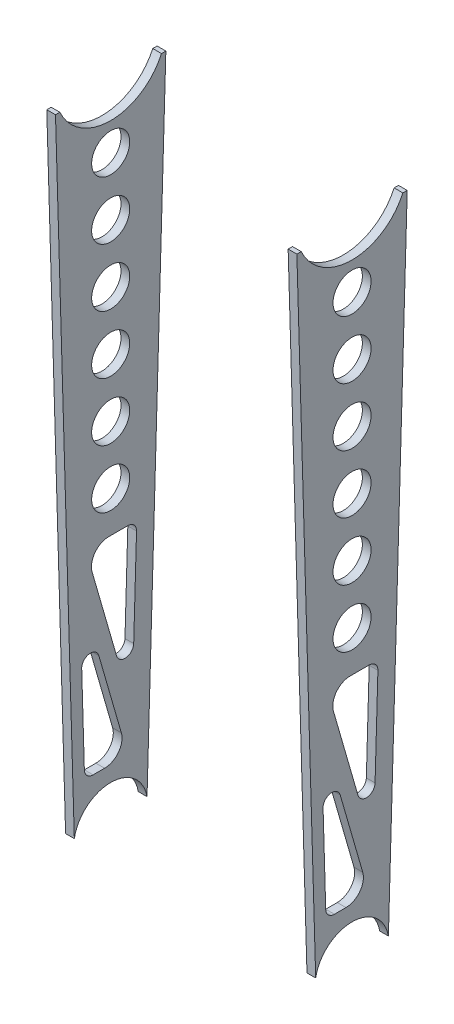
SolidWorks part; units mm, degrees
material "ASTM A36 Steel"
ref_plane "Front Plane" through (0, 0, 0) normal (0, 0, 1) x (1, 0, 0)
ref_plane "Top Plane" through (0, 0, 0) normal (0, 1, 0) x (1, 0, 0)
ref_plane "Right Plane" through (0, 0, 0) normal (1, 0, 0) x (0, 0, -1)
sketch "Sketch1" plane through (0, 0, 0) normal (1, 0, 0) x (0, 0, -1)
  line L0 (-18.9731, -7.9582) -> (-12.5024, -226.7686)
  line L1 (18.9731, -7.9582) -> (12.5024, -226.7686)
  line L2 (-18.9731, -7.9582) -> (-17.4731, -7.9582)
  line L3 (17.4731, -7.9582) -> (18.9731, -7.9582)
  line L4 (0, -22.2) -> (-29.8359, -22.2) construction
  line L5 (0, -19.2) -> (-29.8359, -19.2) construction
  line L10 (-4.0798, -176.4646) -> (3.6669, -203.3381)
  line L11 (-5.4127, -207.8826) -> (7.0583, -207.8826) construction
  line L12 (-5.4127, -207.8826) -> (-11.7157, -142.7546) construction
  line L13 (0, 0) -> (0, -210.55) construction
  line L14 (-11.7157, -142.7546) -> (8.9843, -142.7546) construction
  line L15 (7.0583, -207.8826) -> (8.9843, -142.7546) construction
  line L16 (-5.4127, -207.8826) -> (8.9843, -142.7546) construction
  line L17 (-11.7157, -142.7546) -> (7.0583, -207.8826) construction
  line L18 (-2.0984, -211) -> (-6.0544, -211)
  line L19 (-9.0531, -208.0887) -> (-9.9611, -177.3843)
  line L20 (-0.6196, -142.7546) -> (5.8945, -142.7546)
  line L21 (8.8929, -145.8431) -> (7.9159, -178.8818)
  line L22 (2.0346, -179.6241) -> (-6.3849, -150.4165)
  circle A0 centre (0, 0) radius 19.2 construction
  arc A1 (17.4731, -7.9582) -> (-17.4731, -7.9582) centre (0, 0) cw
  circle A2 centre (0, -48.7494) radius 6.5481
  circle A3 centre (0, -28.7481) radius 6.5481
  circle A6 centre (0, -68.7507) radius 6.5481
  circle A7 centre (0, -88.752) radius 6.5481
  circle A8 centre (0, -108.7533) radius 6.5481
  arc A9 (12.5024, -226.7686) -> (-12.5024, -226.7686) centre (0, -229) ccw
  circle A10 centre (0, -128.7546) radius 6.5481
  arc A11 (-4.0798, -176.4646) -> (-9.9611, -177.3843) centre (-6.9624, -177.2956) ccw
  arc A12 (-6.0544, -211) -> (-9.0531, -208.0887) centre (-6.0544, -208) cw
  arc A13 (3.6669, -203.3381) -> (-2.0984, -211) centre (-2.0984, -205) cw
  arc A14 (7.9159, -178.8818) -> (2.0346, -179.6241) centre (4.9172, -178.7932) cw
  arc A15 (5.8945, -142.7546) -> (8.8929, -145.8431) centre (5.8945, -145.7544) cw
  arc A16 (-0.6196, -142.7546) -> (-6.3849, -150.4165) centre (-0.6196, -148.7546) ccw
  point P5 (12.8535, -227.9864)
  point P36 (0, -183.3969)
  point P49 (-10.6637, -153.6246)
  point P55 (11.6666, -207.8826)
  point P58 (7.3488, -198.0594)
  point P64 (-8.5935, -142.7546)
  dimension "D1" = 38.4
  dimension "D2" = 3
  dimension "D4" = 13.0962
  dimension "D5" = 14
  dimension "D7" = 3
  dimension "D9" = 18
  dimension "D10" = 4
  dimension "D11" = 229
  dimension "D12" = 25.4
  dimension "D13" = 6
  dimension "D14" = 6
  dimension "D19" = 3
  dimension "D21" = 3
  dimension "D8" = 6
  dimension "D3" = 6
  dimension "D6" = 1.5
  dimension "D20" = 2
extrude "Boss-Extrude2" add sketch "Sketch1<2>" against normal blind 3 separate body
sketch "Sketch1<2>" plane through (0, 0, 0) normal (1, 0, 0) x (0, 0, -1) same geometry as "Sketch1"
extrude "Boss-Extrude1" add sketch "Sketch1" along normal blind 3 from offset 80 separate body
sketch "Sketch2" plane through (0, 0, 0) normal (1, 0, 0) x (0, 0, -1)
  circle A0 centre (0, -28.7481) radius 6.5481 construction
  circle A2 centre (0, -28.7481) radius 6.5481
extrude "Boss-ExtrudeUpperBolt" [suppressed] add sketch "Sketch2" along normal blind 102 and the other way blind 12 from offset 6 separate body offset against normal yes
sketch "Sketch4" plane through (0, 0, 0) normal (1, 0, 0) x (0, 0, -1)
  circle A1 centre (0, -88.752) radius 6.5481 construction
  circle A2 centre (0, -88.752) radius 6.5481
extrude "Boss-ExtrudeLowerBolt" [suppressed] add sketch "Sketch4" along normal blind 102 and the other way blind 11 from offset 6 separate body offset against normal yes
sketch "Sketch5" [suppressed] plane through (0, 0, 0) normal (0, 0, 1) x (1, 0, 0)
  line L0 (40, -30.1232) -> (40, -87.2746) construction
  line L1 (1.9, -87.2746) -> (78.1, -87.2746) construction
  line L2 (1.9, -70.4294) -> (1.9, -109.7306)
  line L3 (78.1, -70.4294) -> (78.1, -109.7306)
  line L5 (14.6, -18.3564) -> (14.6, -41.89)
  line L6 (65.4, -18.3564) -> (65.4, -41.89)
  line L7 (0, -7.9577) -> (80, -7.9577) construction
  line L8 (14.6, -30.1232) -> (65.4, -30.1232) construction
  line L9 (40, -7.9577) -> (40, -30.1232) construction
  dimension "D1" = 76.2
  dimension "D2" = 50.8
split line "Split Line1" [suppressed]
sketch "Sketch6" [suppressed] plane through (0, 0, 0) normal (1, 0, 0) x (0, 0, -1)
  circle A0 centre (0, 0) radius 19.2 construction
  circle A2 centre (0, 0) radius 19.2
  circle A3 centre (0, -229) radius 12.7
  circle A4 centre (0, 0) radius 17.2
  circle A5 centre (0, -229) radius 10.7
  dimension "D1" = 2
  dimension "D2" = 2
  dimension "D3" = 25.4
extrude "Boss-ExtrudeCrossTubes" [suppressed] add sketch "Sketch6" along normal blind 192 and the other way blind 328
